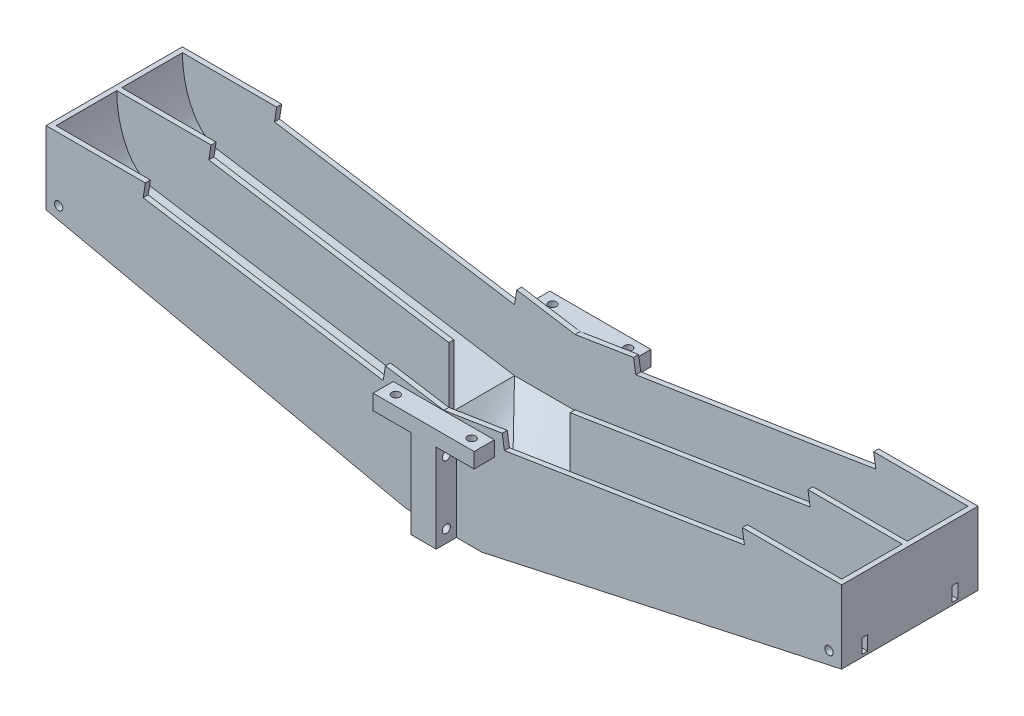
SolidWorks part; units mm, degrees
ref_plane "Front Plane" through (0, 0, 0) normal (0, 0, 1) x (1, 0, 0)
ref_plane "Top Plane" through (0, 0, 0) normal (0, 1, 0) x (1, 0, 0)
ref_plane "Right Plane" through (0, 0, 0) normal (1, 0, 0) x (0, 0, -1)
sketch "Sketch1" plane through (0, 0, 0) normal (0, 1, 0) x (1, 0, 0)
  line L1 (-157.5, -27) -> (157.5, -27)
  line L2 (-157.5, -27) -> (-157.5, 27)
  line L3 (-157.5, 27) -> (157.5, 27)
  line L4 (157.5, -27) -> (157.5, 27)
  line L5 (-157.5, -27) -> (157.5, 27) construction
  line L6 (-157.5, 27) -> (157.5, -27) construction
  point P0 (0, 0)
  dimension "D2" = 315
  dimension "D1" = 54
extrude "Boss-Extrude2" add sketch "Sketch1" along normal blind 60
sketch "Sketch7" plane through (0, 0, 0) normal (0, 0, 1) x (1, 0, 0)
  line L0 (-155.5, 60) -> (-155.5, 36) construction
  line L1 (-141.5, 33.7643) -> (-24, 15)
  line L2 (-157.5, 60) -> (157.5, 60) construction
  line L3 (141.5, 33.7643) -> (24, 15)
  line L4 (-155.5, 36) -> (0, 11.1673) construction
  line L5 (0, 11.1673) -> (155.5, 36) construction
  line L6 (155.5, 36) -> (155.5, 60) construction
  line L7 (155.5, 60) -> (-155.5, 60)
  line L8 (-157.5, 60) -> (-157.5, 0) construction
  line L9 (157.5, 60) -> (157.5, 0) construction
  line L10 (0, 60) -> (0, 0) construction
  line L12 (-24, 15) -> (24, 15)
  line L13 (-157.5, 0) -> (157.5, 0) construction
  ellipse E0 centre (-140.0618, 60) end of major axis (-140.0618, 33.6497) minor radius 15.4382 (-141.5, 33.7643) -> (-155.5, 60) cw
  ellipse E1 centre (140.0618, 60) end of major axis (140.0618, 86.3503) minor radius 15.4382 (155.5, 60) -> (141.5, 33.7643) cw
  dimension "D1" = 2
  dimension "D2" = 2
  dimension "D3" = 24
  dimension "D4" = 15
  dimension "D5" = 48
  dimension "D6" = 16
extrude "Cut-Extrude2" cut sketch "Sketch7" along normal offset from surface 2 and the other way offset from surface 2 up to face at (0, 30, 27) other way up to face at (0, 30, -27)
extrude "Boss-Extrude3" add sketch "Sketch7<2>" along normal mid plane 2
sketch "Sketch7<2>" plane through (0, 0, 0) normal (0, 0, 1) x (1, 0, 0) same geometry as "Sketch7"
sketch "Sketch9" plane through (0, 15, 0) normal (0, 1, 0) x (1, 0, 0)
  line L1 (-24, -25) -> (24, -25)
  line L2 (-24, -25) -> (-24, 25)
  line L3 (-24, 25) -> (24, 25)
  line L4 (24, -25) -> (24, 25)
  line L5 (-24, -25) -> (24, 25) construction
  line L6 (-24, 25) -> (24, -25) construction
  point P0 (0, 0)
extrude "Cut-Extrude5" cut sketch "Sketch9" along normal through all
sketch "Sketch10" plane through (0, 0, 0) normal (0, -1, 0) x (1, 0, 0)
  circle A0 centre (0, 0) radius 13
  dimension "D1" = 26
extrude "Cut-Extrude6" cut sketch "Sketch10" against normal blind 2
sketch "Sketch4" plane through (0, 2, 0) normal (0, -1, 0) x (1, 0, 0)
  circle A0 centre (0, 0) radius 13
  circle A1 centre (0, 0) radius 13 construction
loft "Cut-Loft3" cut profiles "Sketch4", "Sketch9<2>" connector at (0, 2, -13) connector at (-24, 15, -25)
sketch "Sketch9<2>" plane through (0, 15, 0) normal (0, 1, 0) x (1, 0, 0) same geometry as "Sketch9"
sketch "Sketch11" plane through (0, 0, 27) normal (0, 0, 1) x (1, 0, 0)
  line L0 (-157.5, 31.1167) -> (-15, 0)
  line L1 (-157.5, 60) -> (-157.5, 0) construction
  line L2 (-157.5, 0) -> (157.5, 0) construction
  line L3 (-15, 0) -> (-157.5, 0)
  line L4 (-157.5, 0) -> (-157.5, 31.1167)
  line L5 (157.5, 31.1167) -> (157.5, 0)
  line L6 (157.5, 60) -> (157.5, 0) construction
  line L7 (157.5, 0) -> (15, 0)
  line L8 (15, 0) -> (157.5, 31.1167)
  line L9 (-118.1608, 60) -> (-119.042, 54.4819)
  line L10 (-24, 60) -> (-155.5, 60) construction
  line L11 (-119.042, 54.4819) -> (-24, 39.3041)
  line L12 (-118.1608, 60) -> (118.1608, 60)
  line L13 (155.5, 60) -> (24, 60) construction
  line L14 (-141.5, 33.7643) -> (-24, 15) construction
  line L15 (0, 60) -> (0, 0) construction
  line L16 (-141.5, 33.7643) -> (-24, 15) construction
  line L17 (118.1608, 60) -> (119.042, 54.4819)
  line L18 (119.042, 54.4819) -> (24, 39.3041)
  line L19 (-24, 39.3041) -> (-23.1188, 44.8222)
  line L20 (-23.1188, 44.8222) -> (0, 41.1302)
  line L21 (0, 41.1302) -> (23.1188, 44.8222)
  line L22 (23.1188, 44.8222) -> (24, 39.3041)
  line L23 (-24, 60) -> (-24, 15) construction
  line L24 (-13, 0) -> (13, 0) construction
  line L25 (-13, 0) -> (13, 0) construction
  line L26 (-141.5, 33.7643) -> (-142.78, 27.9024) construction
  line L27 (-152.5, 35) -> (152.5, 35) construction
  line L28 (-157.5, 60) -> (-157.5, 0) construction
  circle A0 centre (-152.5, 35) radius 1.65
  circle A1 centre (152.5, 35) radius 1.65
  point P45 (0, 35)
  dimension "D5" = 3.3
  dimension "D1" = 6
  dimension "D2" = 2
  dimension "D3" = 24
  dimension "D4" = 5.588
  dimension "D6" = 25
  dimension "D7" = 5
extrude "Cut-Extrude7" cut sketch "Sketch11" against normal through all
ref_plane "Plane1" through (0, 0, 19) normal (0, 0, 1) x (1, 0, 0)
sketch "Sketch12" plane through (0, 0, 19) normal (0, 0, 1) x (1, 0, 0)
  line L0 (-157.5, 60) -> (-157.5, 31.1167) construction
  line L1 (-150.8546, 37.85) -> (-157.5, 37.85)
  line L2 (-157.5, 37.85) -> (-157.5, 32.15)
  line L3 (157.5, 37.85) -> (157.5, 32.15)
  line L4 (-157.5, 32.15) -> (-150.8546, 32.15)
  line L5 (-150.8546, 32.15) -> (-149.2091, 35)
  line L6 (-149.2091, 35) -> (-150.8546, 37.85)
  line L7 (150.8546, 37.85) -> (149.2091, 35)
  line L8 (149.2091, 35) -> (150.8546, 32.15)
  line L9 (150.8546, 32.15) -> (157.5, 32.15)
  line L10 (157.5, 60) -> (157.5, 31.1167) construction
  line L12 (157.5, 37.85) -> (150.8546, 37.85)
  line L13 (-153.7857, 38.4731) -> (-155.104, 36.1897) [skipped]
  line L14 (-156.1507, 35.6231) -> (-154.8323, 33.3397) [skipped]
  line L15 (156.3932, 33.9568) -> (154.9682, 36.425) [skipped]
  line L16 (154.1454, 32.15) -> (154.9682, 33.575) [skipped]
  circle A0 centre (-152.5, 35) radius 2.85 construction
  circle A1 centre (152.5, 35) radius 2.85 construction
  dimension "D1" = 5.7
extrude "Cut-Extrude8" cut sketch "Sketch12" against normal blind 2.3
ref_plane "Plane2" through (0, 0, -19) normal (0, 0, -1) x (-1, 0, 0)
sketch "Sketch13" plane through (0, 0, -19) normal (0, 0, -1) x (-1, 0, 0)
  line L1 (-150.8546, 37.85) -> (-157.5, 37.85)
  line L2 (-157.5, 37.85) -> (-157.5, 32.15)
  line L3 (157.5, 37.85) -> (157.5, 32.15)
  line L4 (-157.5, 32.15) -> (-150.8546, 32.15)
  line L5 (-150.8546, 32.15) -> (-149.2091, 35)
  line L6 (-149.2091, 35) -> (-150.8546, 37.85)
  line L7 (150.8546, 37.85) -> (149.2091, 35)
  line L8 (149.2091, 35) -> (150.8546, 32.15)
  line L9 (150.8546, 32.15) -> (157.5, 32.15)
  line L11 (157.5, 60) -> (157.5, 31.1167) construction
  line L12 (157.5, 37.85) -> (150.8546, 37.85)
  line L13 (-153.7857, 38.4731) -> (-155.104, 36.1897) [skipped]
  line L14 (-156.1507, 35.6231) -> (-154.8323, 33.3397) [skipped]
  line L15 (156.3932, 33.9568) -> (154.9682, 36.425) [skipped]
  line L16 (154.1454, 32.15) -> (154.9682, 33.575) [skipped]
  line L17 (-157.5, 60) -> (-157.5, 31.1167) construction
  circle A0 centre (-152.5, 35) radius 2.85 construction
  circle A1 centre (152.5, 35) radius 2.85 construction
  circle A3 centre (-152.5, 35) radius 1.65 construction
  circle A4 centre (-152.5, 35) radius 1.65 construction
  circle A5 centre (152.5, 35) radius 1.65 construction
  circle A6 centre (152.5, 35) radius 1.65 construction
  dimension "D1" = 5.7
extrude "Cut-Extrude9" cut sketch "Sketch13" against normal blind 2.3
ref_plane "Plane3" through (0, 35, 0) normal (0, 1, 0) x (1, 0, 0)
sketch "Sketch14" plane through (0, 35, 0) normal (0, 1, 0) x (1, 0, 0)
  line L0 (-23.1188, 27) -> (0, 27) construction
  line L1 (-20, 27) -> (20, 27)
  line L2 (-20, 27) -> (-20, 35)
  line L3 (-20, 35) -> (20, 35)
  line L4 (20, 27) -> (20, 35)
  line L5 (-23.1188, -27) -> (0, -27) construction
  line L6 (-20, -27) -> (20, -27)
  line L7 (-20, -27) -> (-20, -35)
  line L8 (-20, -35) -> (20, -35)
  line L9 (20, -27) -> (20, -35)
  line L10 (0, 35) -> (0, -35) construction
  point P17 (0, 0)
  point P18 (0, 35)
  dimension "D1" = 8
  dimension "D2" = 40
extrude "Boss-Extrude4" add sketch "Sketch14" along normal blind 6
sketch "Sketch15" plane through (0, 0, 0) normal (0, 1, 0) x (1, 0, 0)
  line L0 (-20, 27) -> (20, 27) construction
  line L1 (-5, 27) -> (5, 27)
  line L2 (-5, 27) -> (-5, 35)
  line L3 (-5, 35) -> (5, 35)
  line L4 (5, 27) -> (5, 35)
  line L5 (20, 35) -> (-20, 35) construction
  line L6 (-20, -35) -> (20, -35) construction
  line L7 (-5, -35) -> (5, -35)
  line L8 (-5, -35) -> (-5, -27)
  line L9 (-5, -27) -> (5, -27)
  line L10 (5, -35) -> (5, -27)
  line L11 (20, -27) -> (-20, -27) construction
  line L12 (0, 27) -> (0, -27) construction
  point P16 (0, -27)
  point P21 (0, 0)
  point P22 (0, 27)
  dimension "D1" = 10
extrude "Boss-Extrude5" add sketch "Sketch15" along normal up to surface (35 mm away) up to face at (0, 35, 31)
sketch "Sketch16" plane through (-5, 0, 0) normal (-1, 0, 0) x (0, 0, 1)
  line L0 (-27, 17.5) -> (-35, 17.5) construction
  line L1 (-27, 35) -> (-27, 0) construction
  line L2 (-35, 35) -> (-35, 0) construction
  line L3 (27, 17.5) -> (35, 17.5) construction
  line L5 (27, 35) -> (27, 0) construction
  line L6 (35, 35) -> (35, 0) construction
  line L7 (-31, 30) -> (-31, 5) construction
  line L8 (31, 30) -> (31, 5) construction
  circle A0 centre (-31, 30) radius 1.6
  circle A1 centre (-31, 5) radius 1.6
  circle A2 centre (31, 30) radius 1.6
  circle A3 centre (31, 5) radius 1.6
  point P15 (-31, 17.5)
  point P18 (31, 17.5)
  dimension "D1" = 3.2
  dimension "D2" = 25
extrude "Cut-Extrude10" cut sketch "Sketch16" against normal through all
sketch "Sketch17" plane through (0, 41, 0) normal (0, 1, 0) x (1, 0, 0)
  line L0 (-20, 31) -> (20, 31) construction
  line L1 (-20, 35) -> (-20, 27) construction
  line L2 (20, 27) -> (20, 35) construction
  line L3 (-20, -31) -> (20, -31) construction
  line L4 (-20, -27) -> (-20, -35) construction
  line L5 (20, -35) -> (20, -27) construction
  line L7 (-15, -31) -> (15, -31) construction
  line L8 (-15, -31) -> (-15, 31) construction
  line L9 (-15, 31) -> (15, 31) construction
  line L10 (15, -31) -> (15, 31) construction
  line L11 (-15, -31) -> (15, 31) construction
  line L12 (-15, 31) -> (15, -31) construction
  circle A0 centre (-15, 31) radius 1.6
  circle A1 centre (15, 31) radius 1.6
  circle A2 centre (-15, -31) radius 1.6
  circle A3 centre (15, -31) radius 1.6
  point P12 (0, 0)
  dimension "D1" = 3.2
  dimension "D2" = 30
extrude "Cut-Extrude11" cut sketch "Sketch17" against normal up to surface (6 mm away) up to face at (-12.5, 35, 31)
